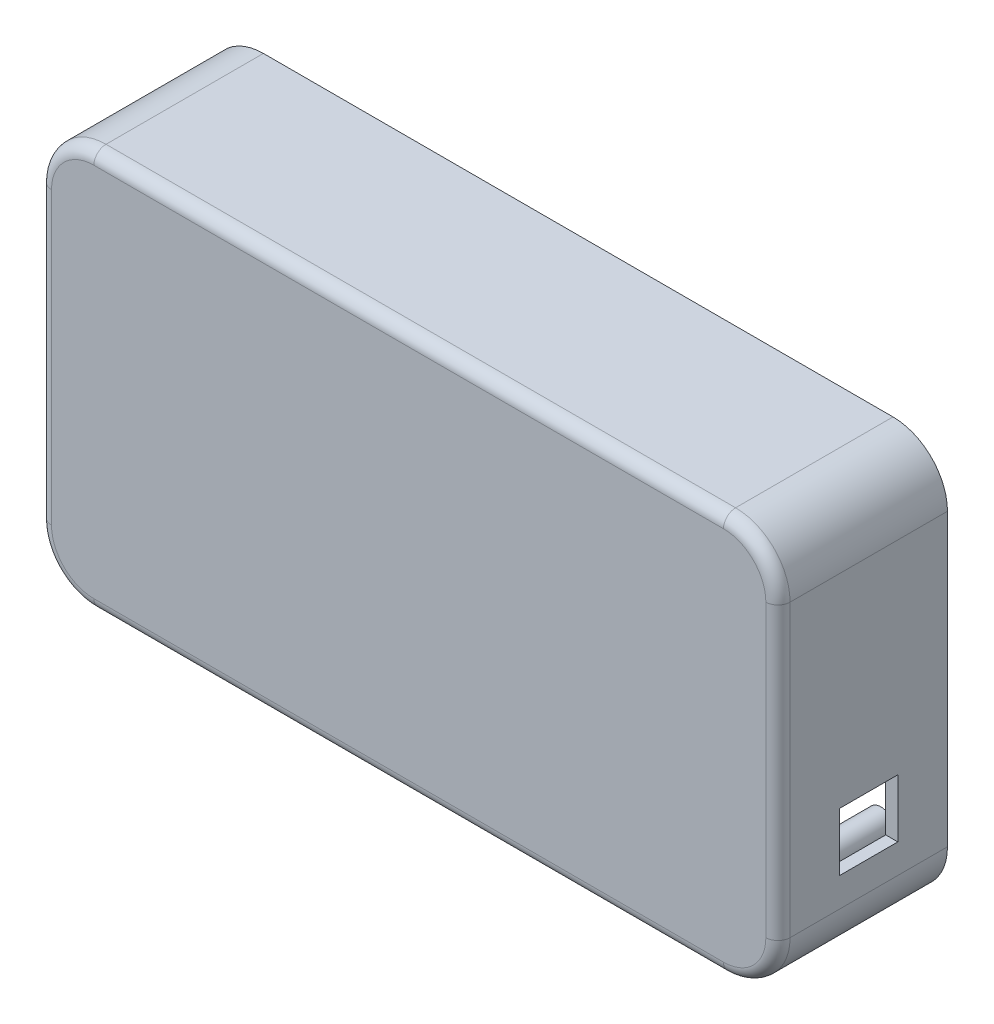
SolidWorks part; units mm, degrees
material "交联聚乙烯"
ref_plane "前视基准面" through (0, 0, 0) normal (0, 0, 1) x (1, 0, 0)
ref_plane "上视基准面" through (0, 0, 0) normal (0, 1, 0) x (1, 0, 0)
ref_plane "右视基准面" through (0, 0, 0) normal (1, 0, 0) x (0, 0, -1)
sketch "草图1" plane through (0, 0, 0) normal (0, 0, 1) x (1, 0, 0)
  line L1 (-130, 82.5) -> (130, 82.5)
  line L2 (-152.5, 60) -> (-152.5, -60)
  line L3 (-130, -82.5) -> (130, -82.5)
  line L4 (152.5, 60) -> (152.5, -60)
  line L5 (0, -82.5) -> (0, 82.5) construction
  line L6 (-152.5, 0) -> (152.5, 0) construction
  line L14 (-130, 77.5) -> (130, 77.5)
  line L15 (147.5, 60) -> (147.5, -60)
  line L16 (-130, -77.5) -> (130, -77.5)
  line L17 (-147.5, 60) -> (-147.5, -60)
  line L18 (-150.2, 60) -> (-150.2, -60)
  line L19 (-130, -80.2) -> (130, -80.2)
  line L20 (150.2, 60) -> (150.2, -60)
  line L21 (-130, 80.2) -> (130, 80.2)
  arc A0 (-130, -82.5) -> (-152.5, -60) centre (-130, -60) cw
  arc A1 (130, -82.5) -> (152.5, -60) centre (130, -60) ccw
  arc A2 (152.5, 60) -> (130, 82.5) centre (130, 60) ccw
  arc A3 (-152.5, 60) -> (-130, 82.5) centre (-130, 60) cw
  arc A12 (147.5, 60) -> (130, 77.5) centre (130, 60) ccw
  arc A13 (130, -77.5) -> (147.5, -60) centre (130, -60) ccw
  arc A14 (-130, -77.5) -> (-147.5, -60) centre (-130, -60) cw
  arc A15 (-147.5, 60) -> (-130, 77.5) centre (-130, 60) cw
  circle A16 centre (130, 60) radius 2.55
  circle A17 centre (130, 60) radius 5.55
  circle A18 centre (130, -60) radius 2.55
  circle A19 centre (130, -60) radius 5.55
  circle A20 centre (-130, 60) radius 2.55
  circle A21 centre (-130, 60) radius 5.55
  circle A22 centre (-130, -60) radius 2.55
  circle A23 centre (-130, -60) radius 5.55
  arc A24 (-130, -80.2) -> (-150.2, -60) centre (-130, -60) cw
  arc A25 (130, -80.2) -> (150.2, -60) centre (130, -60) ccw
  arc A26 (150.2, 60) -> (130, 80.2) centre (130, 60) ccw
  arc A27 (-150.2, 60) -> (-130, 80.2) centre (-130, 60) cw
  point P0 (0, 0)
  point P6 (-152.5, -82.5)
  point P9 (152.5, -82.5)
  point P12 (152.5, 82.5)
  dimension "D3" = 22.5
  dimension "D6" = 5.1
  dimension "D8" = 5.1
  dimension "D10" = 5.1
  dimension "D12" = 5.1
  dimension "D1" = 305
  dimension "D2" = 165
  dimension "D4" = 2.3
  dimension "D7" = 3
  dimension "D9" = 3
  dimension "D11" = 3
  dimension "D13" = 3
extrude "凸台-拉伸1" add sketch "草图1" along normal blind 70 contours A3 L1 A2 L4 A1 L3 A0 L2
extrude "切除-拉伸1" cut sketch "草图1<4>" along normal blind 65 contours A15 L17 A14 L16 A13 L15 A12 L14 region at (0, 0, 0)
sketch "草图1<4>" plane through (0, 0, 0) normal (0, 0, 1) x (1, 0, 0) same geometry as "草图1"
sketch "草图3" plane through (0, 0, 0) normal (0, 0, -1) x (-1, 0, 0)
extrude "切除-拉伸2" cut sketch "草图1<5>" along normal blind 5 contours A27 L21 A26 L20 A25 L19 A24 L18 L17 A15 L14 A12 L15 A13 L16 A14 region at (-144.0428, 74.0428, 0)
sketch "草图1<5>" plane through (0, 0, 0) normal (0, 0, 1) x (1, 0, 0) same geometry as "草图1"
extrude "切除-拉伸3" cut sketch "草图1<6>" along normal blind 5 contours A17 A16 region at (124.607, 60, 0)
sketch "草图1<6>" plane through (0, 0, 0) normal (0, 0, 1) x (1, 0, 0) same geometry as "草图1"
extrude "切除-拉伸4" cut sketch "草图1<7>" along normal blind 40 contours A16 region at (130, 60, 0)
sketch "草图1<7>" plane through (0, 0, 0) normal (0, 0, 1) x (1, 0, 0) same geometry as "草图1"
extrude "切除-拉伸5" cut sketch "草图1<8>" along normal blind 40 contours A18 region at (130, -60, 0)
sketch "草图1<8>" plane through (0, 0, 0) normal (0, 0, 1) x (1, 0, 0) same geometry as "草图1"
extrude "切除-拉伸6" cut sketch "草图1<10>" along normal blind 40 contours A22 region at (-130, -60, 0)
sketch "草图1<10>" plane through (0, 0, 0) normal (0, 0, 1) x (1, 0, 0) same geometry as "草图1"
extrude "切除-拉伸7" cut sketch "草图1<11>" along normal blind 40 contours A20 region at (-130, 60, 0)
sketch "草图1<11>" plane through (0, 0, 0) normal (0, 0, 1) x (1, 0, 0) same geometry as "草图1"
extrude "切除-拉伸8" cut sketch "草图1<12>" along normal blind 5 contours A21 A20 region at (-135.393, 60, 0)
sketch "草图1<12>" plane through (0, 0, 0) normal (0, 0, 1) x (1, 0, 0) same geometry as "草图1"
extrude "切除-拉伸9" cut sketch "草图1<13>" along normal blind 5 contours A23 A22 region at (-135.393, -60, 0)
sketch "草图1<13>" plane through (0, 0, 0) normal (0, 0, 1) x (1, 0, 0) same geometry as "草图1"
extrude "切除-拉伸10" cut sketch "草图1<14>" along normal blind 5 contours A19 A18 region at (124.607, -60, 0)
sketch "草图1<14>" plane through (0, 0, 0) normal (0, 0, 1) x (1, 0, 0) same geometry as "草图1"
fillet "圆角2" radius 5 4 edges at (-152.5, 0, 70) (0, -82.5, 70) (152.5, 0, 70) (0, 82.5, 70) type face fillet first side face at (0, 0, 70) second side face at (-152.5, 0, 35) second side face at (0, -82.5, 35) second side face at (152.5, 0, 35) second side face at (0, 82.5, 35)
sketch3d "3D草图1"
  point P0 (44.0813, -82.5, 36.7135)
sketch "草图14" plane through (0, -82.5, 0) normal (0, -1, 0) x (1, 0, 0)
  line L0 (-130, 65) -> (130, 65) construction
  line L5 (0, 58) -> (9, 58) construction
  line L6 (0, 65.0893) -> (0, 54.1873) construction
  line L8 (-6, 54.5) -> (6, 54.5)
  line L9 (-6, 54.5) -> (-6, 61.5)
  line L10 (-6, 61.5) -> (6, 61.5)
  line L11 (6, 54.5) -> (6, 61.5)
  line L12 (0, 61.5) -> (0, 54.5) construction
  line L13 (-6, 58) -> (6, 58) construction
  circle A0 centre (9, 58) radius 1.6
  circle A1 centre (-9, 58) radius 1.6
  point P0 (0, 58)
  dimension "D5" = 3.2
  dimension "D1" = 12
  dimension "D2" = 7
  dimension "D3" = 7
  dimension "D4" = 9
extrude "切除-拉伸11" cut sketch "草图14" against normal blind 5
sketch "草图16" plane through (152.5, 0, 0) normal (1, 0, 0) x (0, 0, -1)
  line L1 (-32.5, 60.9225) -> (-32.5, 24.0444) construction
  line L2 (-65, 60) -> (0, 60) construction
  line L3 (-44.5, -24) -> (-20.5, -24)
  line L4 (-44.5, -24) -> (-44.5, -48)
  line L5 (-44.5, -48) -> (-20.5, -48)
  line L6 (-20.5, -24) -> (-20.5, -48)
  line L7 (-32.5, -48) -> (-32.5, -24) construction
  line L8 (-44.5, -36) -> (-20.5, -36) construction
  line L9 (-65, -60) -> (0, -60) construction
  point P0 (-32.5, -36)
  point P8 (-32.5, 60)
  point P11 (-32.5, -60)
  dimension "D1" = 24
  dimension "D2" = 24
  dimension "D3" = 12
extrude "切除-拉伸12" cut sketch "草图16" against normal blind 5
sketch "草图18" plane through (-152.5, 0, 0) normal (-1, 0, 0) x (0, 0, 1)
  line L1 (32.5, 62.5) -> (32.5, 54.0347) construction
  line L2 (65, 60) -> (0, 60) construction
  line L3 (65, -60) -> (0, -60) construction
  line L4 (20.5, -24) -> (44.5, -24)
  line L5 (20.5, -24) -> (20.5, -48)
  line L6 (20.5, -48) -> (44.5, -48)
  line L7 (44.5, -24) -> (44.5, -48)
  line L8 (32.5, -48) -> (32.5, -24) construction
  line L9 (20.5, -36) -> (44.5, -36) construction
  point P2 (32.5, 60)
  point P4 (32.5, -36)
  point P11 (32.5, -60)
  dimension "D1" = 24
  dimension "D2" = 24
  dimension "D3" = 12
extrude "切除-拉伸13" cut sketch "草图18" against normal blind 5
sketch "草图19" plane through (0, 0, 65) normal (0, 0, -1) x (-1, 0, 0)
  line L0 (-103, 36) -> (-18, 36) construction
  line L1 (-103, 40) -> (-18, 40)
  line L2 (-103, 32) -> (-18, 32)
  line L3 (152.5, 0) -> (-152.5, 0) construction
  line L4 (0, -82.5) -> (0, 82.5) construction
  line L5 (-147.5, 0) -> (-107.2295, 0) construction
  line L6 (0, 77.5) -> (0, 61.8371) construction
  line L7 (103, 36) -> (18, 36) construction
  line L8 (103, 40) -> (18, 40)
  line L9 (103, 32) -> (18, 32)
  line L10 (-103, -24) -> (-23, -24) construction
  line L11 (-103, -20) -> (-23, -20)
  line L12 (-103, -28) -> (-23, -28)
  line L14 (103, -24) -> (23, -24) construction
  line L15 (103, -20) -> (23, -20)
  line L16 (103, -28) -> (23, -28)
  arc A0 (-103, 40) -> (-103, 32) centre (-103, 36) ccw
  arc A1 (-18, 32) -> (-18, 40) centre (-18, 36) ccw
  arc A2 (103, 40) -> (103, 32) centre (103, 36) cw
  arc A3 (18, 32) -> (18, 40) centre (18, 36) cw
  arc A4 (-103, -20) -> (-103, -28) centre (-103, -24) ccw
  arc A5 (-23, -28) -> (-23, -20) centre (-23, -24) ccw
  arc A6 (103, -20) -> (103, -28) centre (103, -24) cw
  arc A7 (23, -28) -> (23, -20) centre (23, -24) cw
  point P2 (-60.5, 36)
  point P13 (60.5, 36)
  point P23 (-63, -24)
  point P33 (63, -24)
  dimension "D2" = 4
  dimension "D7" = 4
  dimension "D8" = 80
  dimension "D1" = 85
  dimension "D3" = 18
  dimension "D4" = 32
  dimension "D5" = 23
  dimension "D6" = 20
extrude "凸台-拉伸2" add sketch "草图19" along normal blind 60
sketch "草图28" plane through (0, 0, 5) normal (0, 0, -1) x (-1, 0, 0)
  line L0 (103, -22) -> (23, -22) construction
  line L1 (103, -20) -> (23, -20) construction
  line L2 (23, -22) -> (23, -20) construction
  line L3 (103, -22) -> (103, -20) construction
  arc A0 (23, -20) -> (23, -28) centre (23, -24) ccw construction
  text T0 "<b>P P G E K I</b>" font "微软雅黑" height 3
  dimension "D1" = 2
extrude "字" cut sketch "草图28" against normal blind 1
sketch "草图29" plane through (0, 0, 65) normal (0, 0, -1) x (-1, 0, 0)
  line L0 (14.35, -45.2) -> (-14.35, -45.2)
  line L1 (12.85, -43.7) -> (-12.85, -43.7)
  line L2 (12.85, -43.7) -> (12.85, -20)
  line L3 (12.85, -20) -> (-12.85, -20)
  line L4 (-12.85, -43.7) -> (-12.85, -20)
  line L5 (0, -20) -> (0, -43.7) construction
  line L6 (12.85, -31.85) -> (-12.85, -31.85) construction
  line L7 (0, -41.7182) -> (0, 1.1541) construction
  line L8 (-14.35, -45.2) -> (-14.35, -18.5)
  line L9 (14.35, -18.5) -> (-14.35, -18.5)
  line L10 (17.8546, 0) -> (-23.7773, 0) construction
  line L11 (14.35, -45.2) -> (14.35, -18.5)
  line L12 (0, -31.85) -> (-17.5, -31.85) construction
  line L14 (-30, 20) -> (30, 20) construction
  line L15 (-30, 20) -> (-30, -10) construction
  line L16 (-30, -10) -> (30, -10) construction
  line L17 (30, 20) -> (30, -10) construction
  line L18 (0, -10) -> (0, 20) construction
  line L19 (-30, 5) -> (30, 5) construction
  circle A0 centre (-17.5, -31.85) radius 1.1
  circle A1 centre (-17.5, -31.85) radius 3
  circle A2 centre (17.5, -31.85) radius 1.1
  circle A3 centre (17.5, -31.85) radius 3
  circle A4 centre (-30, 20) radius 1.1
  circle A5 centre (30, 20) radius 1.1
  circle A6 centre (30, -10) radius 1.1
  circle A7 centre (-30, -10) radius 1.1
  circle A8 centre (-30, 20) radius 3.1
  circle A9 centre (30, 20) radius 3.1
  circle A10 centre (30, -10) radius 3.1
  circle A11 centre (-30, -10) radius 3.1
  point P0 (0, -31.85)
  point P21 (0, 0)
  dimension "D6" = 2.2
  dimension "D10" = 2.2
  dimension "D11" = 2.2
  dimension "D12" = 2.2
  dimension "D13" = 2.2
  dimension "D1" = 23.7
  dimension "D2" = 25.7
  dimension "D3" = 20
  dimension "D5" = 17.5
  dimension "D8" = 60
  dimension "D9" = 30
  dimension "D15" = 5
  dimension "D4" = 1.5
  dimension "D7" = 1.9
  dimension "D14" = 2
extrude "凸台-拉伸3" add sketch "草图29" along normal blind 2 contours L0 L11 L9 L8 L1 L4 L3 L2 region at (0, -44.808, 65)
extrude "凸台-拉伸4" add sketch "草图29<4>" along normal blind 5 contours A1 A0 | A3 A2 region at (20.4151, -31.85, 65) region at (-14.5849, -31.85, 65)
sketch "草图29<4>" plane through (0, 0, 65) normal (0, 0, -1) x (-1, 0, 0) same geometry as "草图29"
extrude "凸台-拉伸5" add sketch "草图29<5>" along normal blind 6.5 contours A8 A4 | A11 A7 | A9 A5 | A10 A6 region at (33.0123, 20, 65) region at (-26.9877, 20, 65) region at (-26.9877, -10, 65) region at (33.0123, -10, 65)
sketch "草图29<5>" plane through (0, 0, 65) normal (0, 0, -1) x (-1, 0, 0) same geometry as "草图29"
